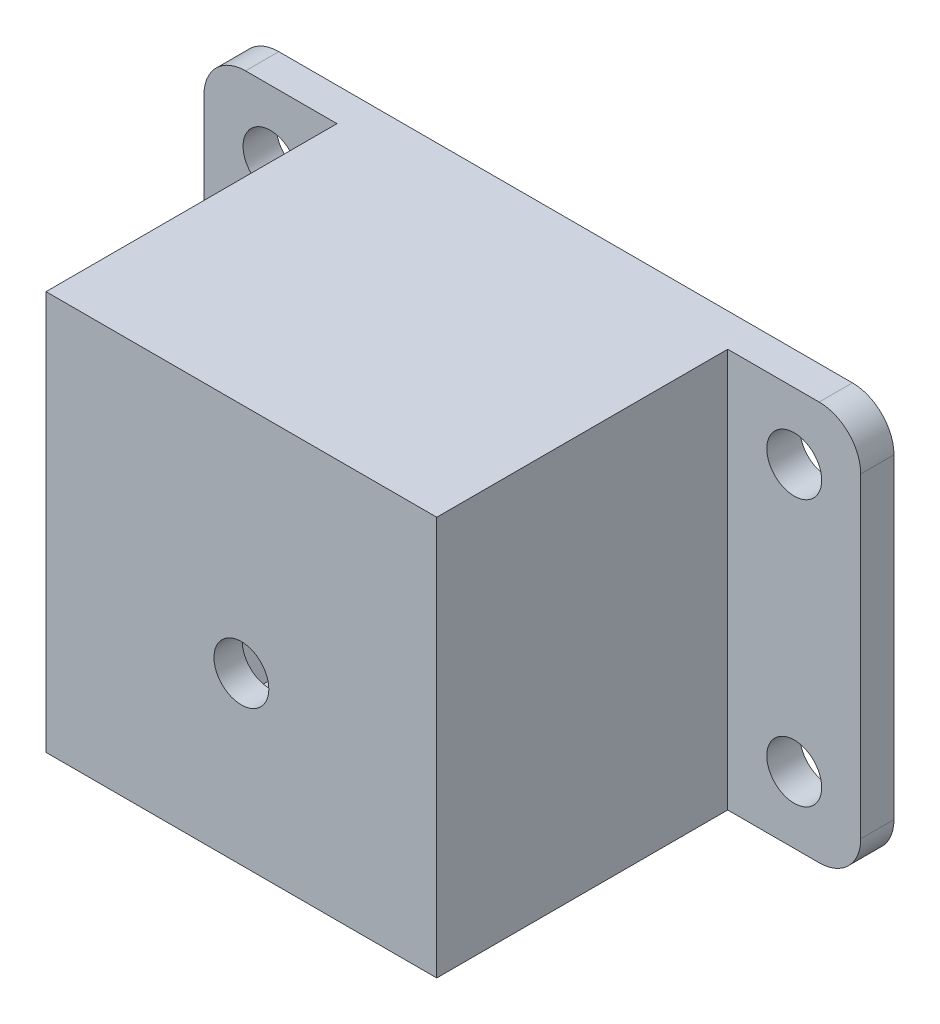
SolidWorks part; units mm, degrees
ref_plane "Front Plane" through (0, 0, 0) normal (1, 0, 0) x (0, 1, 0)
ref_plane "Top Plane" through (0, 0, 0) normal (0, 0, 1) x (0, 1, 0)
ref_plane "Right Plane" through (0, 0, 0) normal (0, 1, 0) x (-1, 0, 0)
sketch "Sketch1" plane through (0, 0, 0) normal (0, 0, 1) x (0, 1, 0)
  line L0 (-24, 12) -> (-4, 12)
  line L1 (0, 0) -> (-24, 0)
  line L2 (0, 0) -> (0, 39.5)
  line L3 (0, 39.5) -> (-24, 39.5)
  line L4 (-24, 0) -> (-24, 12)
  line L5 (-4, 12) -> (-4, 27.5)
  line L6 (-4, 27.5) -> (-24, 27.5)
  line L7 (-24, 27.5) -> (-24, 39.5)
  circle A0 centre (-20, 4) radius 1.65
  circle A1 centre (-4, 4) radius 1.65
  circle A2 centre (-4, 35.5) radius 1.65
  circle A3 centre (-20, 35.5) radius 1.65
  dimension "D1" = 3.3
  dimension "D4" = 20
  dimension "D5" = 4
  dimension "D7" = 20
  dimension "D9" = 4
  dimension "D11" = 4
  dimension "D12" = 20
  dimension "D2" = 15.5
  dimension "D3" = 12
  dimension "D6" = 4
  dimension "D8" = 12
  dimension "D10" = 4
extrude "Boss-Extrude1" add sketch "Sketch1" along normal blind 2
sketch "Sketch2" plane through (0, 0, 2) normal (0, 0, 1) x (1, 0, 0)
  line L0 (-27.5, -24) -> (-27.5, -4)
  line L1 (-27.5, -4) -> (-12, -4)
  line L2 (-12, -4) -> (-12, -24)
  line L3 (-12, -24) -> (-8, -24)
  line L4 (-12, -24) -> (0, -24) construction
  line L5 (-8, -24) -> (-8, 0)
  line L6 (0, 0) -> (-39.5, 0) construction
  line L7 (-8, 0) -> (-31.5, 0)
  line L8 (-31.5, 0) -> (-31.5, -24)
  line L9 (-39.5, -24) -> (-27.5, -24) construction
  line L10 (-31.5, -24) -> (-27.5, -24)
  dimension "D1" = 4
  dimension "D2" = 4
extrude "Boss-Extrude2" add sketch "Sketch2" along normal blind 11.5
sketch "Sketch3" plane through (0, 0, 13.5) normal (0, 0, 1) x (1, 0, 0)
  line L1 (-31.5, 0) -> (-8, 0)
  line L2 (-31.5, 0) -> (-31.5, -24)
  line L3 (-31.5, -24) -> (-8, -24)
  line L4 (-8, 0) -> (-8, -24)
  circle A0 centre (-19.75, -14) radius 1.65
  point P8 (-19.75, 0)
  point P9 (0, 0)
  dimension "D1" = 3.3
  dimension "D2" = 10
extrude "Boss-Extrude3" add sketch "Sketch3" along normal blind 6
sketch "Sketch4" plane through (0, 0, 19.5) normal (0, 0, 1) x (1, 0, 0)
  line L1 (-16.4014, -14) -> (-18.0757, -11.1)
  line L2 (-18.0757, -11.1) -> (-21.4243, -11.1)
  line L3 (-21.4243, -11.1) -> (-23.0986, -14)
  line L4 (-23.0986, -14) -> (-21.4243, -16.9)
  line L5 (-21.4243, -16.9) -> (-18.0757, -16.9)
  line L6 (-18.0757, -16.9) -> (-16.4014, -14)
  circle A0 centre (-19.75, -14) radius 2.9 construction
  dimension "D1" = 5.8
extrude "Cut-Extrude1" cut sketch "Sketch4" against normal blind 2.6 from offset 1.7 offset against normal yes
fillet "Fillet1" radius 2.5 4 edges at (0, -24, 1) (0, 0, 1) (-39.5, 0, 1) (-39.5, -24, 1)
